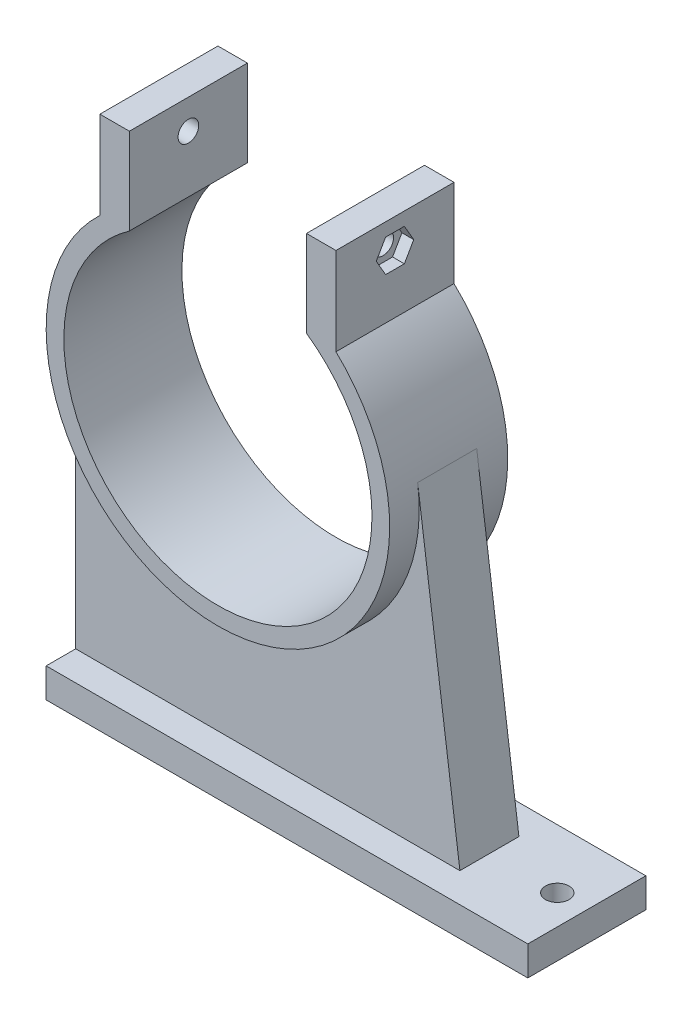
SolidWorks part; units mm, degrees
material "PET"
ref_plane "Piano frontale" through (0, 0, 0) normal (0, 0, 1) x (1, 0, 0)
ref_plane "Piano superiore" through (0, 0, 0) normal (0, 1, 0) x (1, 0, 0)
ref_plane "Piano destro" through (0, 0, 0) normal (1, 0, 0) x (0, 0, -1)
sketch "Schizzo1" plane through (0, 0, 0) normal (0, 0, 1) x (1, 0, 0)
  circle A2 centre (0, 0) radius 26.1
  circle A3 centre (0, 0) radius 29.1
  point P2 (0, -27.7328)
  point P11 (0, 0)
  point P16 (0, 0)
  point P17 (-15, 21.2352)
  dimension "D1" = 52.2
  dimension "D2" = 3
extrude "Estrusione-Estrusione1" add sketch "Schizzo1" along normal blind 20
sketch "Schizzo2" plane through (0, 0, 20) normal (0, 0, 1) x (1, 0, 0)
  line L0 (-15, 27.3999) -> (15, 27.3999) construction
  line L1 (-15, 36) -> (-20, 36)
  line L2 (-15, 36) -> (-15, 18.7997)
  line L3 (-15, 18.7997) -> (-20, 18.7997)
  line L4 (-20, 36) -> (-20, 18.7997)
  line L5 (15, 36) -> (20, 36)
  line L6 (15, 36) -> (15, 18.7997)
  line L7 (15, 18.7997) -> (20, 18.7997)
  line L8 (20, 36) -> (20, 18.7997)
  point P8 (-15, 27.3999)
  point P9 (15, 27.3999)
  point P10 (0, 27.3999)
  dimension "D1" = 30
  dimension "D2" = 5
  dimension "D3" = 36
extrude "Estrusione-Estrusione2" add sketch "Schizzo2" against normal up to surface (20 mm away) up to face at (29.1, 0, 0)
sketch "Schizzo3" plane through (0, 0, 20) normal (0, 0, 1) x (1, 0, 0)
  line L0 (15, 21.3591) -> (15, 18.7997) construction
  line L1 (-15, 36) -> (15, 36)
  line L2 (-15, 36) -> (-15, 19.0896)
  line L3 (-15, 19.0896) -> (15, 19.0896)
  line L4 (15, 36) -> (15, 19.0896)
extrude "Taglio-Estrusione1" cut sketch "Schizzo3" against normal through all
sketch "Schizzo4" plane through (0, 0, 20) normal (0, 0, 1) x (1, 0, 0)
  arc A0 (-18.1047, 18.7997) -> (18.1047, 18.7997) centre (0, 0) ccw construction
  arc A1 (-18.1047, 18.7997) -> (18.1047, 18.7997) centre (0, 0) ccw
  circle A2 centre (0, 0) radius 26.1
  line M2 (-15, 18.7997) -> (-15, 36)
  line M8 (15, 36) -> (15, 18.7997)
  line M9 (15, 18.7997) -> (18.1047, 18.7997)
  arc M10 (18.1047, 18.7997) -> (-18.1047, 18.7997) centre (0, 0) cw
  line M11 (-18.1047, 18.7997) -> (-15, 18.7997)
extrude "Taglio-Estrusione3" cut sketch "Schizzo4" against normal through all contours A2 M8 M2 M11 M10 M9 | A2 M2 M11 | A2 M9 M8 region at (0, -0.0772, 20) region at (-16.0617, 19.6753, 20) region at (16.0617, 19.6753, 20)
sketch "Schizzo5" plane through (-20, 0, 0) normal (-1, 0, 0) x (0, 0, 1)
  line L0 (0, 26) -> (20, 26) construction
  line L1 (0, 21.1379) -> (0, 36) construction
  line L2 (20, 36) -> (20, 21.1379) construction
  line L3 (0, 36) -> (20, 26) construction
  circle A0 centre (10, 31) radius 1.75
  dimension "D2" = 3.5
  dimension "D1" = 26
extrude "Taglio-Estrusione4" cut sketch "Schizzo5" against normal through all
sketch "Schizzo6" plane through (-20, 0, 0) normal (-1, 0, 0) x (0, 0, 1)
  circle A0 centre (10, 31) radius 3.25
  dimension "D1" = 6.5
extrude "Taglio-Estrusione5" cut sketch "Schizzo6" against normal blind 2
sketch "Schizzo7" plane through (20, 0, 0) normal (1, 0, 0) x (0, 0, -1)
  line L1 (-8.4123, 28.25) -> (-6.8246, 31)
  line L2 (-6.8246, 31) -> (-8.4123, 33.75)
  line L3 (-8.4123, 33.75) -> (-11.5877, 33.75)
  line L4 (-11.5877, 33.75) -> (-13.1754, 31)
  line L5 (-13.1754, 31) -> (-11.5877, 28.25)
  line L6 (-11.5877, 28.25) -> (-8.4123, 28.25)
  circle A0 centre (-10, 31) radius 2.75 construction
  dimension "D1" = 5.5
extrude "Taglio-Estrusione6" cut sketch "Schizzo7" against normal blind 2
sketch "Schizzo8" plane through (0, 0, 0) normal (0, 0, -1) x (-1, 0, 0)
  line L0 (-52.5, -54.5) -> (29.1, -54.5)
  line L1 (29.1, -54.5) -> (29.1, 0)
  line L2 (-52.5, -54.5) -> (-52.5, -49.5)
  line L3 (-52.5, -49.5) -> (-36, -49.5)
  line L4 (-36, -49.5) -> (-28.8417, 3.8685)
  line L5 (-28.8417, 3.8685) -> (29.1, 0)
  arc A0 (-20, 21.1379) -> (20, 21.1379) centre (0, 0) ccw
  arc A3 (-20, 21.1379) -> (20, 21.1379) centre (0, 0) ccw construction
  arc M5 (15, 21.3591) -> (-15, 21.3591) centre (0, 0) cw
  arc M9 (-20, 21.1379) -> (20, 21.1379) centre (0, 0) ccw
  dimension "D1" = 54.5
  dimension "D2" = 52.5
  dimension "D3" = 5
  dimension "D4" = 36
extrude "Estrusione-Estrusione3" add sketch "Schizzo8" against normal blind 10 from offset 5 contours L4 L3 L2 L0 L1 M9 | L5 M9 M5 region at (4.8443, -38.3055, 0) region at (1.894, -28.368, 0) offset against normal yes
sketch "Schizzo10" plane through (0, 0, 5) normal (0, 0, -1) x (-1, 0, 0)
  line L1 (-52.5, -49.5) -> (29.1, -49.5)
  line L2 (-52.5, -49.5) -> (-52.5, -54.5)
  line L3 (-52.5, -54.5) -> (29.1, -54.5)
  line L4 (29.1, -49.5) -> (29.1, -54.5)
extrude "Estrusione-Estrusione4" add sketch "Schizzo10" against normal blind 20 from offset 5
sketch "Schizzo9" plane through (0, -49.5, 0) normal (0, 1, 0) x (1, 0, 0)
  line L0 (52.5, -10) -> (47.5, -10)
  line L1 (52.5, -20) -> (52.5, 0) construction
  circle A0 centre (47.5, -10) radius 2
  dimension "D2" = 4
  dimension "D1" = 5
extrude "Taglio-Estrusione7" cut sketch "Schizzo9" against normal through all contours A0 region at (45.5566, -49.5, 10)
